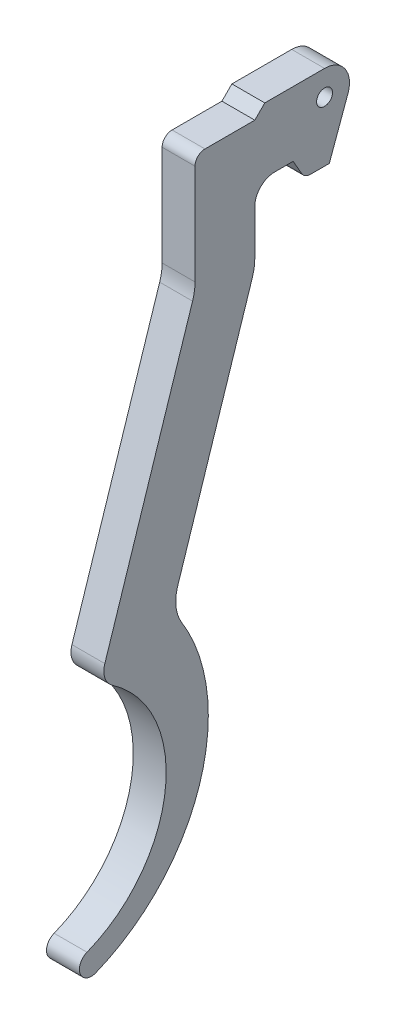
SolidWorks part; units mm, degrees
ref_plane "Front Plane" through (0, 0, 0) normal (0, 0, 1) x (1, 0, 0)
ref_plane "Top Plane" through (0, 0, 0) normal (0, 1, 0) x (1, 0, 0)
ref_plane "Right Plane" through (0, 0, 0) normal (1, 0, 0) x (0, 0, -1)
sketch "Sketch1" plane through (0, 0, 0) normal (1, 0, 0) x (0, 0, -1)
  circle A0 centre (0, 0) radius 2.5
  circle A1 centre (0, 0) radius 0.8
  dimension "D1" = 5
  dimension "D2" = 1.6
extrude "Boss-Extrude1" add sketch "Sketch1" along normal blind 1.65 and the other way blind 1.65
sketch "Sketch2" plane through (1.65, 0, 0) normal (1, 0, 0) x (0, 0, -1)
  line L0 (2.3492, -0.8551) -> (0.4766, -6)
  line L1 (0.4766, -6) -> (-13, -6)
  line L6 (-7, 2.5) -> (0, 2.5)
  line L7 (-7, 2.5) -> (-7, 1.5)
  line L8 (-7, 1.5) -> (-13, 1.5)
  line L9 (-13, 1.5) -> (-13, -6)
  circle A0 centre (0, 0) radius 2.5 construction
  circle A1 centre (0, 0) radius 0.8 construction
  circle A2 centre (0, 0) radius 2.5
  arc A3 (2.3492, -0.8551) -> (0, 2.5) centre (0, 0) ccw
  circle A4 centre (0, 0) radius 0.8
  dimension "D2" = 70
  dimension "D3" = 7
  dimension "D4" = 1
  dimension "D5" = 8.5
  dimension "D6" = 6
  dimension "D1" = 0
extrude "Boss-Extrude2" add sketch "Sketch2" against normal blind 3.3
sketch "Sketch3" plane through (1.65, 0, 0) normal (1, 0, 0) x (0, 0, -1)
  line L0 (-13, -6) -> (0.4766, -6) construction
  line L1 (-13, -6) -> (-2, -6)
  line L2 (-13, -6) -> (-13, -4)
  line L3 (-13, -4) -> (-3.1547, -4)
  line L4 (-2, -6) -> (-3.1547, -4)
  dimension "D1" = 2
  dimension "D2" = 60
  dimension "D3" = 11
extrude "Cut-Extrude1" cut sketch "Sketch3" against normal blind 4
chamfer "Chamfer1" distance 1 angle 45 1 edges at (0, 2.5, 7)
fillet "Fillet2" radius 1 1 edges at (0, -6, 2)
sketch "Sketch4" plane through (1.65, 0, 0) normal (1, 0, 0) x (0, 0, -1)
  line L6 (-13, -4) -> (-13, -10.3497)
  line L7 (-13, -10.3497) -> (-22.5365, -39.7)
  line L8 (-13, -4) -> (-7, -4)
  line L9 (-3.1547, -4) -> (-13, -4) construction
  line L10 (-7, -4) -> (-7, -11.3)
  line L11 (-7, -11.3) -> (-15.3504, -37)
  line L12 (-13, 1.5) -> (-13, -4) construction
  arc A0 (-22.5365, -39.7) -> (-23.8374, -62.3826) centre (-28.394, -50.7426) cw
  arc A1 (-23.8374, -62.3826) -> (-22.9525, -64.6134) centre (-23.4, -63.5) ccw
  arc A2 (-15.3504, -37) -> (-22.9525, -64.6134) centre (-29.6657, -47.9121) cw
  dimension "D6" = 12.5
  dimension "D7" = 18
  dimension "D9" = 1.2
  dimension "D2" = 6
  dimension "D3" = 7.3
  dimension "D4" = 33
  dimension "D5" = 6
  dimension "D8" = 59.5
  dimension "D10" = 10.4
  dimension "D11" = 108
  dimension "D12" = 35.7
extrude "Boss-Extrude3" add sketch "Sketch4" against normal blind 3.3
fillet "Fillet3" radius 2 1 edges at (0, -39.7, 22.5365)
fillet "Fillet4" radius 4 1 edges at (0, -37, 15.3504)
fillet "Fillet5" radius 5 1 edges at (0, -11.3, 7)
fillet "Fillet6" radius 5 1 edges at (0, -10.3497, 13)
fillet "Fillet7" radius 2 1 edges at (0, -4, 7)
fillet "Fillet8" radius 1 1 edges at (0, 1.5, 13)
